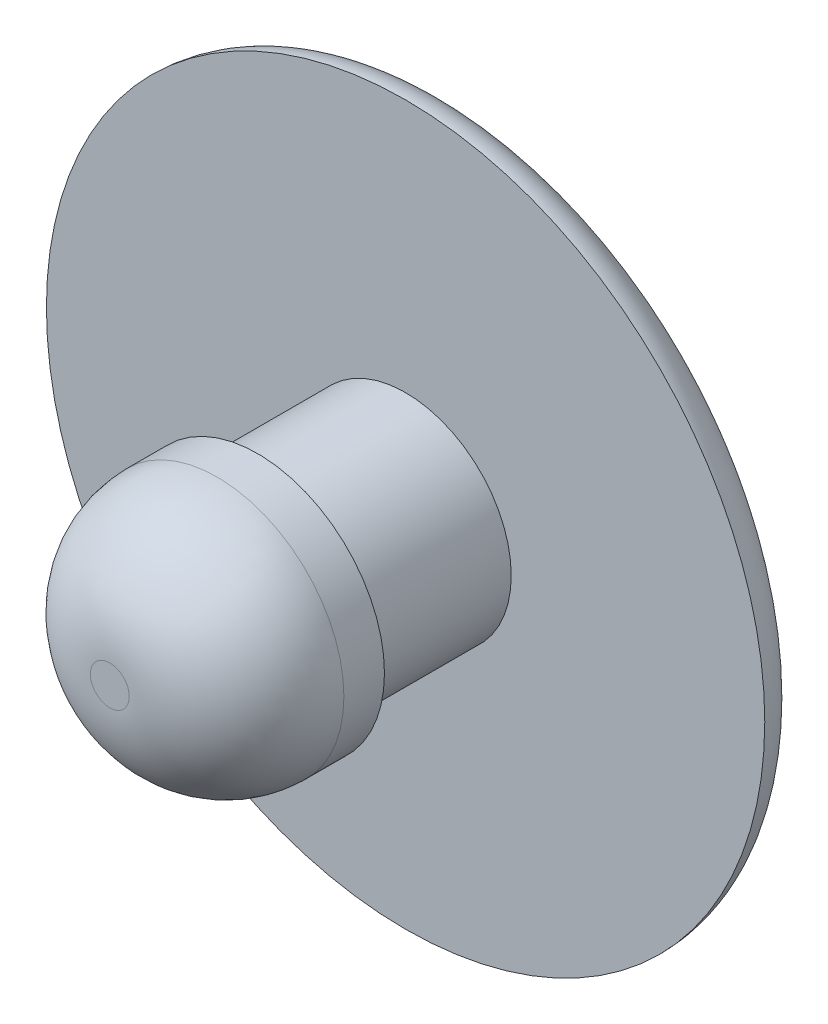
SolidWorks part; units mm, degrees
ref_plane "Front Plane" through (0, 0, 0) normal (0, 0, 1) x (1, 0, 0)
ref_plane "Top Plane" through (0, 0, 0) normal (0, 1, 0) x (1, 0, 0)
ref_plane "Right Plane" through (0, 0, 0) normal (1, 0, 0) x (0, 0, -1)
sketch "Sketch1" plane through (0, 0, 0) normal (0, 0, 1) x (1, 0, 0)
  circle A0 centre (0, 0) radius 4.25
  dimension "D1" = 8.5
extrude "Boss-Extrude1" add sketch "Sketch1" along normal blind 0.5
fillet "Fillet1" radius 0.508 1 edges at (4.25, 0, 0)
sketch "Sketch2" plane through (0, 0, 0.5) normal (0, 0, 1) x (1, 0, 0)
  circle A0 centre (0, 0) radius 1.25
  dimension "D1" = 2.5
extrude "Boss-Extrude2" add sketch "Sketch2" along normal blind 1.75
sketch "Sketch3" plane through (0, 0, 2.25) normal (0, 0, 1) x (1, 0, 0)
  circle A0 centre (0, 0) radius 1.5
  dimension "D1" = 3
extrude "Boss-Extrude3" add sketch "Sketch3" along normal blind 1.75
fillet "Fillet2" radius 1.27 1 edges at (1.5, 0, 4)
